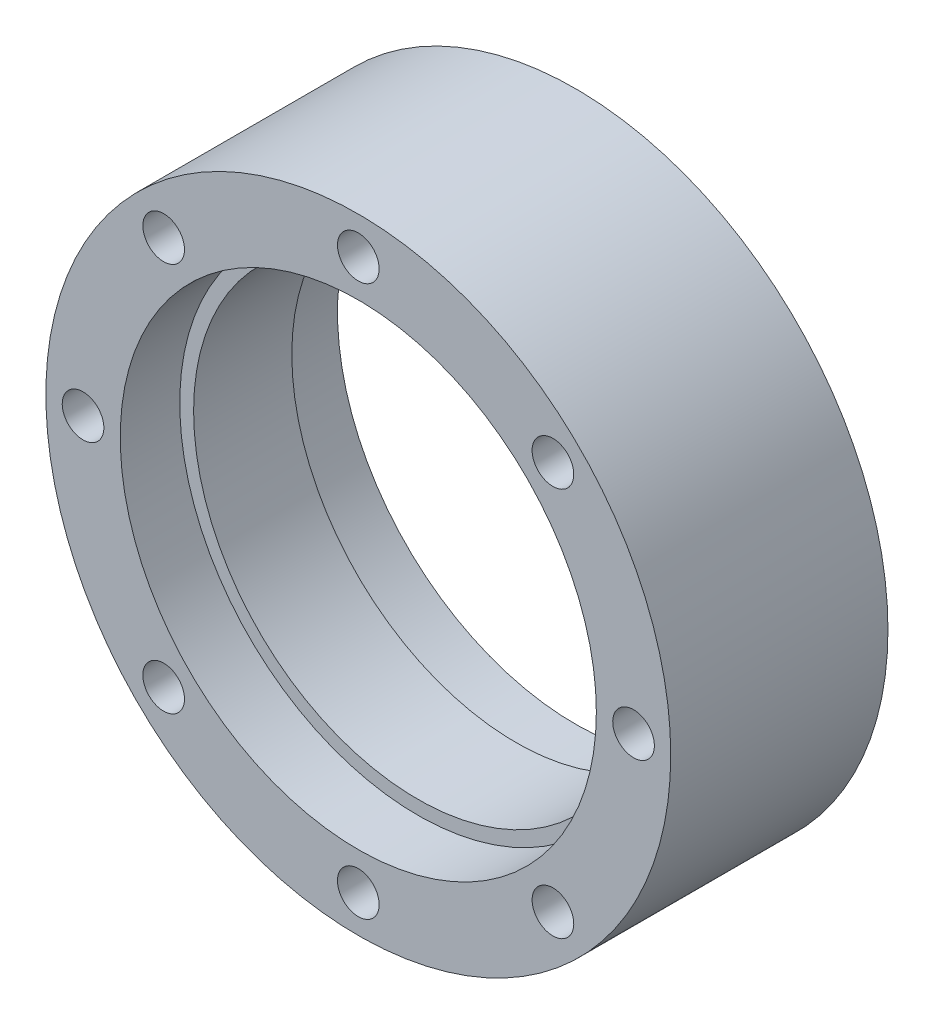
SolidWorks part; units mm, degrees
ref_plane "Front Plane" through (0, 0, 0) normal (0, 0, 1) x (1, 0, 0)
ref_plane "Top Plane" through (0, 0, 0) normal (0, 1, 0) x (1, 0, 0)
ref_plane "Right Plane" through (0, 0, 0) normal (1, 0, 0) x (0, 0, -1)
ref_axis "Z" through (0, 0, 8.03) along (0, 0, -1)
sketch "Sketch7" plane through (0, 0, 0) normal (0, 1, 0) x (1, 0, 0)
  line L0 (16, 7.3) -> (16, 3.3)
  line L2 (16, 3.3) -> (15.07, 3.3)
  line L5 (16, 7.3) -> (21, 7.3)
  line L6 (21, 7.3) -> (21, -7.3)
  line L7 (24.7452, 0) -> (-6.4078, 0) construction
  line L8 (16, -3.3) -> (15.07, -3.3)
  line L9 (16, -7.3) -> (16, -3.3)
  line L10 (15.07, 3.3) -> (15.07, -3.3)
  line L11 (21, -7.3) -> (16, -7.3)
  line L12 (0, -8.03) -> (0, 8.03) construction
  dimension "D2" = 4
  dimension "D4" = 3.3
  dimension "D1" = 15.07
  dimension "D3" = 16
  dimension "D5" = 21
revolve "Revolve1" add sketch "Sketch7" angle 360 about axis through (0, 0, 8.03) along (0, 0, -1)
sketch "Sketch3" plane through (0, 0, 0) normal (0, 0, 1) x (1, 0, 0)
  line L0 (0, 0) -> (0, 18.5) construction
  circle A0 centre (0, 18.5) radius 1.4
  dimension "D1" = 2.8
  dimension "D2" = 18.5
extrude "Cut-Extrude2" cut sketch "Sketch3" against normal through all both and the other way through all
sketch "Sketch4" plane through (0, 0, -7.3) normal (0, 0, -1) x (-1, 0, 0)
  circle A0 centre (0, 18.5) radius 2.35
  circle A1 centre (0, 18.5) radius 1.4 construction
  dimension "D1" = 4.7
extrude "Cut-Extrude4" cut sketch "Sketch4" against normal blind 2.5 and the other way through all
chamfer "Chamfer1" distance 0.1 angle 45 1 edges at (-1.4, 18.5, -4.8)
pattern_circular "CirPattern3" count 4 over 360 about axis through (0, 0, 8.03) along (0, 0, -1) of "Cut-Extrude4"
pattern_circular "CirPattern2" count 8 over 360 about axis through (0, 0, 8.03) along (0, 0, -1) of "Cut-Extrude2"
equation "\"BearingOD\"= 32"
equation "\"BearingHeight\"= 4"
equation "\"SeatsOD\"= \"BearingOD\" + 10"
equation "\"RetainingRingThickness\"= 1.30"
equation "\"BearingBaseDistance\"= 17.2 - 2*\"BearingHeight\"  - \"RetainingRingThickness\"*2"
equation "\"WireHarnessHeight\"= 4"
equation "\"OuterWallWidth\"= 6"
equation "\"OverallOD\"= 42"
equation "\"BearingID\"= 25"
equation "\"OverallHeight\"= \"WireHarnessHeight\" + \"BearingHeight\"*2 + \"BearingBaseDistance\""
equation "\"RetaininRingGrooveDiameter\"= 23.9"
equation "\"ShaftLengthAfterFlange\"= 2*\"BearingHeight\" + \"BearingBaseDistance\" + \"RetainingRingThickness\"*2\t'give a retaining ring thickness of extra clearance"
equation "\"RetainingRingGrooveBase\"= \"ShaftLengthAfterFlange\" - \"RetainingRingThickness\"*2"
equation "\"CoverThickness\"= 1"
equation "\"CoverClearance\"= 1"
equation "\"FlangHeight\"= 3"
equation "\"OuterHousingHeight\"= \"WireHarnessHeight\" + \"BearingHeight\"*2 + \"BearingBaseDistance\""
equation "\"PCBWidth\"= 5"
equation "\"PCBHeight\"= \"OuterHousingHeight\" "
equation "\"PCBThickness\"= 1"
equation "\"NormalDistSidewallPCBToZ\"= (\"OverallOD\"/2) - 1.6\t'radial distance from the z axis to pcb origin on the top/connector side"
equation "\"PCBSidewallCutoutClearance\"= 0.1"
equation "\"D3@Sketch7\"=\"BearingOD\"/2"
equation "\"D4@Sketch7\"=\"BearingBaseDistance\"/2"
equation "\"D5@Sketch7\"=\"OverallOD\"/2"
equation "\"D2@Sketch3\"=(\"OverallOD\"+\"BearingOD\")/4"
equation "\"OutputHubBoltCircleRadius\"= 8"
equation "\"OutputHubOD\"= 27"
equation "\"BearingInnerRaceOD\"= 26.9"
equation "\"StatorWireRadius\"= \"NormalDistSidewallPCBToZ\" - 5.7"
equation "\"MountingHoleRadius\"= (\"OverallOD\"+\"BearingOD\")/4"
